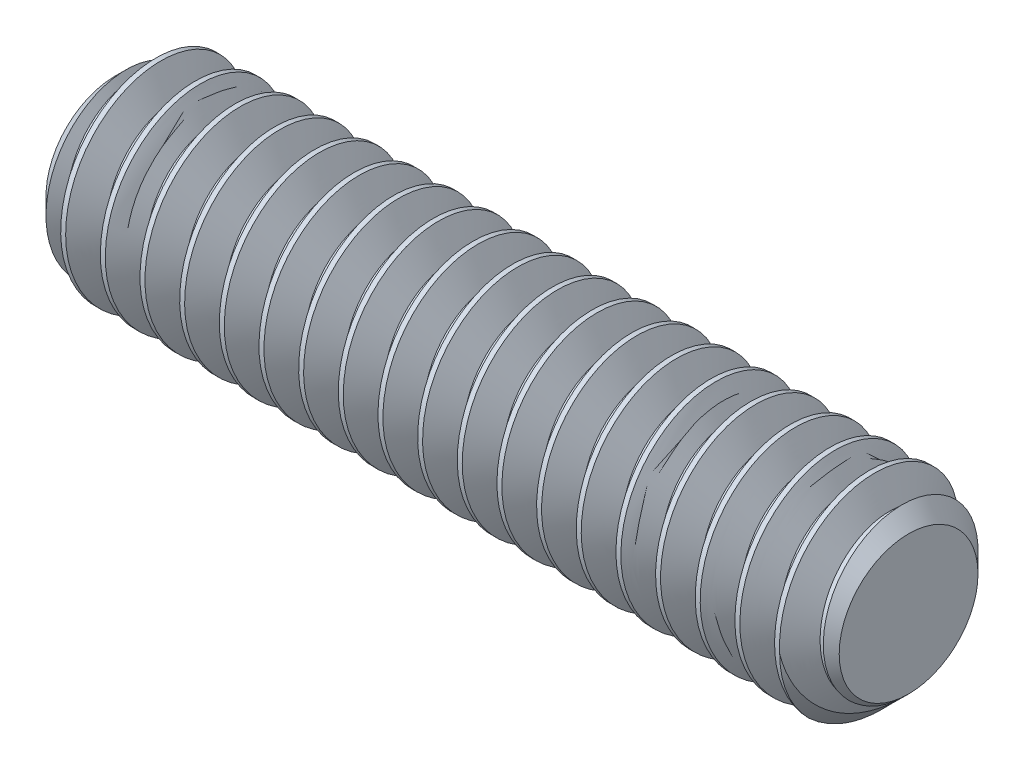
SolidWorks part; units mm, degrees
ref_plane "Front Plane" through (0, 0, 0) normal (0, 0, 1) x (1, 0, 0)
ref_plane "Top Plane" through (0, 0, 0) normal (0, 1, 0) x (1, 0, 0)
ref_plane "Right Plane" through (0, 0, 0) normal (1, 0, 0) x (0, 0, -1)
sketch "Sketch1" plane through (0, 0, 0) normal (0, 0, 1) x (1, 0, 0)
  line L0 (-12.7, 0) -> (12.7, 0) construction
  line L1 (12.7, 3.175) -> (12.7, -3.175) construction
  line L2 (-12.7, 3.175) -> (-12.7, -3.175) construction
  point P6 (8.255, -3.175)
  dimension "D1" = 4.445
  dimension "Thread Diameter" = 6.35
  dimension "Length" = 25.4
sketch "Sketch2" plane through (0, 0, 0) normal (1, 0, 0) x (0, 0, -1)
  circle A0 centre (0, 0) radius 3.175
extrude "Boss-Extrude1" add sketch "Sketch2" against normal up to vertex (12.7 mm away) and the other way up to vertex (12.7 mm away) up to point (-12.7, 0, 0) other way up to point (12.7, 0, 0)
sketch "Sketch3" plane through (12.7, 0, 0) normal (1, 0, 0) x (0, 0, -1)
  circle A1 centre (0, 0) radius 3.175
  circle A2 centre (0, 0) radius 3.175
  dimension "D1" = 0
curve "Helix/Spiral1" pitch 1.27 height 26.67 turns 21 parameters "Pitch"=1.27
chamfer "Chamfer1" distance 0.9525 angle 45 2 edges at (-12.7, 0, -3.175) (12.7, 0, -3.175)
sketch "Sketch4" plane through (0, 0, 0) normal (0, 0, 1) x (1, 0, 0)
  line L0 (12.6206, 3.3125) -> (13.2556, 2.2126) construction
  line L1 (13.2556, 2.2126) -> (13.8906, 3.3125) construction
  line L2 (13.8906, 3.3125) -> (12.6206, 3.3125) construction
  line L3 (13.2556, 3.3125) -> (13.2556, 3.175) construction
  line L4 (13.2556, 2.2126) -> (13.2556, 2.3501) construction
  line L5 (13.1762, 2.3501) -> (13.335, 2.3501) construction
  line L6 (12.7, 3.175) -> (13.8112, 3.175) construction
  line L7 (13.1762, 2.3501) -> (12.6603, 3.2437)
  line L8 (13.1762, 2.3501) -> (13.335, 2.3501)
  line L9 (12.6603, 3.2437) -> (13.8509, 3.2437)
  line L10 (13.8509, 3.2437) -> (13.335, 2.3501)
  point P13 (13.2556, 3.2437)
  dimension "D1" = 1.27
  dimension "D2" = 0.1588
sweep "Cut-Sweep3" cut profiles "Sketch4" path "Helix/Spiral1"
equation "\"D3@Helix/Spiral1\" = \"Length@Sketch1\"+\"Pitch@Helix/Spiral1\""
equation "\"D1@Chamfer1\" = \"Pitch@Helix/Spiral1\"*.75"
equation "\"D1@Sketch4\" = \"Pitch@Helix/Spiral1\""
equation "\"D2@Sketch4\" = \"D1@Sketch4\"/8"
equation "\"D1@Sketch1\" = \"Pitch@Helix/Spiral1\"*3.50"
